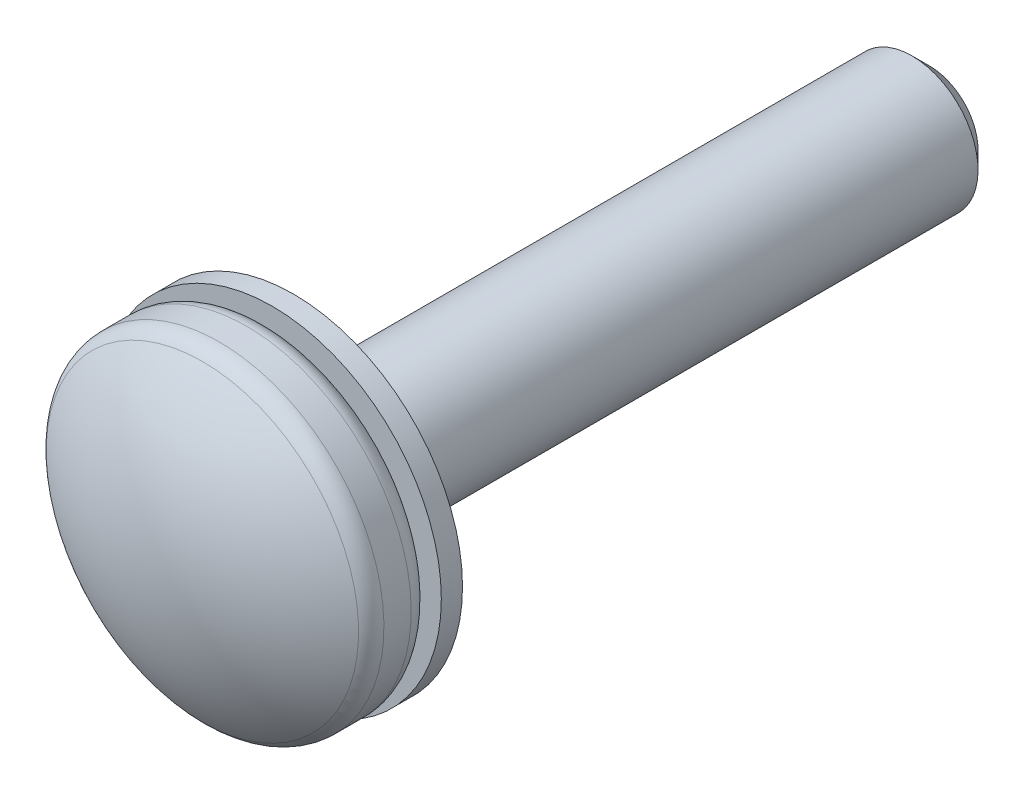
SolidWorks part; units mm, degrees
material "AISI 304"
ref_plane "Front Plane" through (0, 0, 0) normal (0, 0, 1) x (1, 0, 0)
ref_plane "Top Plane" through (0, 0, 0) normal (0, 1, 0) x (1, 0, 0)
ref_plane "Right Plane" through (0, 0, 0) normal (1, 0, 0) x (0, 0, -1)
sketch "Sketch1" plane through (0, 0, 0) normal (0, 0, 1) x (1, 0, 0)
  circle A0 centre (0, 0) radius 2.413
  dimension "decimal equ" = 4.826
curve "Helix/Spiral1" pitch 0.7937 height 19.8438 turns 25 parameters "helix length"=19.8438, "pitch"=0.7937
sketch "Sketch2" plane through (0, 0, 0) normal (1, 0, 0) x (0, 0, -1)
  line L0 (0.2977, 2.413) -> (0.3969, 2.413)
  line L1 (0.3969, 2.413) -> (0.6945, 1.8974)
  line L2 (0.2977, 2.413) -> (0, 1.8974)
  line L3 (0, 1.8974) -> (0.6945, 1.8974)
  line L4 (0, 1.8974) -> (0, 2.413) construction
  line L5 (0, 2.413) -> (0, -2.413) construction
  line L6 (0.1488, 2.1552) -> (0.5457, 2.1552) construction
  line L7 (0, 2.413) -> (0, -2.413) construction
  line L8 (0.3473, 2.413) -> (0.3473, 1.8974) construction
  point P6 (-3.175, -2.413)
  dimension "D1" = 60
  dimension "D3" = 0.0992
  dimension "D4" = 0.3969
  dimension "D2" = 3.175
sketch "Sketch3" plane through (0, 0, 0) normal (1, 0, 0) x (0, 0, -1)
  line L0 (0, 0) -> (-19.05, 0) construction
  line L1 (0, 1.8974) -> (0.6945, 1.8974) construction
  line L2 (0, 0) -> (-19.05, 0)
  line L3 (0, 0) -> (0, 1.8974)
  line L4 (0, 1.8974) -> (-19.05, 1.8974)
  line L5 (-19.05, 0) -> (-19.05, 1.8974)
  dimension "length" = 19.05
revolve "Revolve1" add sketch "Sketch3" angle 360 about L0
sweep "Sweep1" [suppressed] add profiles "Sketch2" path "Helix/Spiral1"
sketch "Sketch33" [suppressed] plane through (0, 0, 0) normal (0, 0, -1) x (-1, 0, 0)
  circle A1 centre (0, 0) radius 2.413
extrude "Extrude6" [suppressed] cut sketch "Sketch33" along normal through all
sketch "Sketch34" [suppressed] plane through (0, 0, 0) normal (0, 0, -1) x (-1, 0, 0)
  circle A0 centre (0, 0) radius 1.8974 construction
  circle A1 centre (0, 0) radius 1.8026
  dimension "D2" = 3.6051
extrude "Extrude7" [suppressed] cut sketch "Sketch34" against normal through all draft 45 flip side to cut
sketch "Sketch10" plane through (0, 0, 0) normal (1, 0, 0) x (0, 0, -1)
  line L0 (0, 0) -> (23.0169, 0) construction
  line L1 (-273.05, 12.7) -> (-19.05, 12.7)
  line L2 (-273.05, 12.7) -> (-273.05, 0)
  line L3 (-273.05, 0) -> (-19.05, 0)
  line L4 (-19.05, 12.7) -> (-19.05, 0)
  line L5 (-19.05, 0) -> (-19.05, 1.8974) construction
  dimension "D1" = 254
  dimension "D2" = 12.7
revolve "Cut-Revolve2" [suppressed] cut sketch "Sketch10" angle 360 about L0
sketch "Sketch35" plane through (0, 0, 0) normal (1, 0, 0) x (0, 0, -1)
  line L0 (-19.05, 2.413) -> (-19.05, 1.8974)
  line L1 (-19.05, 1.8974) -> (-18.1356, 1.8974)
  line L2 (-18.1356, 1.8974) -> (-17.62, 2.413)
  line L3 (-19.05, 2.413) -> (-17.62, 2.413)
  dimension "D1" = 45
  dimension "D2" = 0.9144
revolve "Cut-Revolve4" [suppressed] cut sketch "Sketch35" angle 360 about L2
sketch "Sketch8" plane through (0, 0, 0) normal (1, 0, 0) x (0, 0, -1)
  line L0 (0, 0) -> (-6.2449, 0) construction
  line L1 (-22.4282, 0) -> (-19.05, 0)
  line L2 (-22.4282, 0) -> (-22.4282, 4.7371)
  line L3 (-22.4282, 4.7371) -> (-19.05, 4.7371)
  line L4 (-19.05, 0) -> (-19.05, 4.7371)
  line L5 (-22.4282, -4.7371) -> (-19.05, -4.7371) construction
  line L6 (-19.05, 0) -> (-19.05, 1.8974) construction
  dimension "head dia" = 9.4742
  dimension "head height" = 3.3782
revolve "Revolve2" add sketch "Sketch8" angle 360 about L0
sketch "Sketch11" plane through (0, 0, 0) normal (1, 0, 0) x (0, 0, -1)
  line L0 (-20.7391, 4.7371) -> (-20.7391, -4.0894) construction
  line L1 (-22.4282, 0) -> (-6.8951, 0) construction
  line L2 (-22.4282, 4.7371) -> (-19.05, 4.7371) construction
  line L3 (-22.4282, 0) -> (-22.4282, 4.7371) construction
  line L4 (-20.4431, 4.7371) -> (-19.6581, 4.7371)
  line L6 (-19.05, 0) -> (-19.05, 4.7371) construction
  line L7 (-19.05, 4.129) -> (-18.415, 4.129)
  line L8 (-18.415, 4.129) -> (-18.415, 5.3721)
  line L9 (-18.415, 5.3721) -> (-23.0632, 5.3721)
  line L10 (-23.0632, 5.3721) -> (-23.0632, 0)
  line L11 (-23.0632, 0) -> (-22.4282, 0)
  arc A0 (-20.9295, 4.494) -> (-22.4282, 0) centre (-14.941, 0) ccw
  arc A1 (-19.05, 4.129) -> (-19.6581, 4.7371) centre (-19.6581, 4.129) ccw
  arc A2 (-20.9295, 4.494) -> (-20.4431, 4.7371) centre (-20.4431, 4.129) cw
  dimension "D1" = 0.6081
  dimension "D2" = 0.635
  dimension "D3" = 0.635
  dimension "D4" = 0.635
revolve "Cut-Revolve3" cut sketch "Sketch11" angle 360 about L1
ref_plane "Plane1" through (0, 0, 22.4282) normal (0, 0, 1) x (1, 0, 0)
sketch "Sketch12" plane through (0, 0, 22.4282) normal (0, 0, 1) x (1, 0, 0)
  line L0 (0.508, 2.3264) -> (0.508, 1.1906)
  line L1 (0.508, 1.1906) -> (1.1906, 0.508) construction
  line L2 (1.1906, 0.508) -> (2.3264, 0.508)
  line L3 (0, 2.3813) -> (0, 0)
  line L4 (0, 0) -> (2.3813, 0)
  line L5 (0, 0) -> (0, 4.7371) construction
  line L6 (0, 0) -> (0.8493, 0.8493) construction
  line L7 (1.1906, 0) -> (1.1906, 1.5633) construction
  line L8 (0.508, 1.1906) -> (0.7079, 0.7079)
  line L9 (1.1906, 0.508) -> (0.7079, 0.7079)
  line L10 (0, 0) -> (0, -1.0114) construction
  line L11 (-0.508, 2.3264) -> (-0.508, 1.1906) construction
  arc A0 (2.3813, 0) -> (2.3264, 0.508) centre (0, 0) ccw
  arc A1 (0.508, 2.3264) -> (0, 2.3813) centre (0, 0) ccw
  arc A2 (-2.3813, 0) -> (-2.3264, 0.508) centre (0, 0) cw construction
  dimension "phillips dia" = 4.7625
  dimension "D2" = 45
  dimension "D4" = 22.5
  dimension "slot width" = 1.016
extrude "Cut-Extrude1" [suppressed] cut sketch "Sketch12" against normal blind 2.8715
draft "Draft3" [suppressed] type of draft neutral plane draft angle 15 neutral plane "Plane1" faces to draft 2 parameters "D1"=15
draft "Draft4" [suppressed] type of draft neutral plane draft angle 5 neutral plane "Plane1" faces to draft 4 parameters "D1"=5
pattern_circular "CirPattern1" [suppressed] count 4 over 360 about axis through (0, 0, 22.4282) along (0, 0, -1) of bodies 110
ref_plane "Plane8" through (0, 0, 18.9187) normal (0, 0, -1) x (-1, 0, 0)
sketch "Sketch18" plane through (0, 0, 18.9187) normal (0, 0, 1) x (1, 0, 0)
  line L0 (0, -1.8974) -> (0, -4.8641) construction
  circle A0 centre (0, 0) radius 4.8641
  circle A1 centre (0, 0) radius 1.8974 construction
  circle A3 centre (0, 0) radius 3.3808
  point P10 (0, -3.3808)
  dimension "washer dia." = 9.7282
  dimension "D1" = 2.9667
  dimension "D2" = 1.4833
extrude "Extrude1" add sketch "Sketch18" against normal blind 0.6096 separate body
sketch "Sketch19" plane through (0, 0, 18.3091) normal (0, 0, -1) x (-1, 0, 0)
  line L0 (0, 0) -> (0, 8.8432) construction
  line L1 (1.3953, 3.5272) -> (0, 0)
  line L2 (0.9883, 3.6882) -> (0, 0) construction
  line L3 (0.5552, 3.7523) -> (0, 0)
  line L4 (0.4948, 3.3444) -> (1.2436, 3.1437) construction
  arc A0 (1.3953, 3.5272) -> (0.5552, 3.7523) centre (0.9883, 3.6882) ccw
  circle A1 centre (0, 0) radius 3.3808 construction
  circle A5 centre (0, 0) radius 4.2561
  circle A6 centre (0, 0) radius 4.2561 construction
  dimension "D2" = 0.8755
  dimension "D3" = 15
extrude "Cut-Extrude2" [suppressed] cut sketch "Sketch19" against normal through all
pattern_circular "CirPattern2" [suppressed] count 12 over 360 of bodies 119
ref_plane "Plane6" [suppressed] through (0, 3.3444, 0) normal (0, 1, 0) x (-1, 0, 0)
sketch "Sketch25" [suppressed] plane through (0, 3.3444, 0) normal (0, 1, 0) x (-1, 0, 0)
  line L2 (-0.4948, 18.6139) -> (0.4948, 18.6139) construction
  line L4 (-0.4948, 18.3091) -> (0.4948, 18.3091)
  line L5 (-0.4948, 18.3091) -> (-0.4948, 18.9187)
  line L6 (-0.4948, 18.9187) -> (0.4948, 18.9187)
  line L7 (0.4948, 18.3091) -> (0.4948, 18.9187)
  line L14 (0, 18.6139) -> (0, 18.3091) construction
ref_plane "Plane7" [suppressed] through (0, 1.8974, 0) normal (0, 1, 0) x (-1, 0, 0)
sketch "Sketch26" [suppressed] plane through (0, 1.8974, 0) normal (0, 1, 0) x (-1, 0, 0)
  line L0 (-0.4781, 18.4931) -> (-0.2301, 19.05)
  line L1 (-0.4781, 18.4931) -> (0.2301, 18.1778)
  line L2 (-0.2301, 19.05) -> (0.4781, 18.7347)
  line L3 (0.2301, 18.1778) -> (0.4781, 18.7347)
  line L7 (-0.3541, 18.7716) -> (0.3541, 18.4562) construction
  line L8 (-0.124, 18.3354) -> (0, 18.6139) construction
  line L9 (-0.2301, 19.05) -> (-0.2301, 18.9187) construction
  line L11 (4.8641, 18.9187) -> (-4.8641, 18.9187) construction
  line L13 (0.4781, 18.9187) -> (-0.2301, 18.9187) construction
  line L14 (-0.4948, 18.3091) -> (-0.4948, 18.9187) construction
  line L15 (-0.4948, 18.6139) -> (0.4948, 18.6139) construction
  dimension "D1" = 0.7752
  dimension "D3" = 24
loft "Loft4" [suppressed] add profiles "Sketch25", "Sketch26"
sketch "Sketch30" [suppressed] plane through (0, 3.3444, 0) normal (0, 1, 0) x (-1, 0, 0)
  line L4 (-0.4948, 18.3091) -> (0.4948, 18.3091)
  line L5 (-0.4948, 18.3091) -> (0.4948, 18.3091)
  line L6 (0.4948, 18.3091) -> (0.4948, 18.9187)
  line L7 (0.4948, 18.3091) -> (0.4948, 18.9187)
  line L8 (0.4948, 18.9187) -> (-0.4948, 18.9187)
  line L9 (0.4948, 18.9187) -> (-0.4948, 18.9187)
  line L10 (-0.4948, 18.9187) -> (-0.4948, 18.3091)
  line L11 (-0.4948, 18.9187) -> (-0.4948, 18.3091)
  dimension "D1" = 0
extrude "Extrude5" [suppressed] add sketch "Sketch30" along normal blind 0.0508 separate body
pattern_circular "CirPattern8" [suppressed] count 12 over 360 of bodies 182 144
combine bodies "Combine2" [suppressed] operation type add bodies to combine 144 182 187 188 189 190 191 192 193 194 195 196 197 198 199 200 201 202 203 204 205 206 207 208 120
chamfer "Chamfer1" distance 0.508 angle 45 1 edges at (0, 1.8974, 0)
equation "\"D3@Sketch2\" = \"pitch@Helix/Spiral1\"*.125"
equation "\"D4@Sketch2\" = \"pitch@Helix/Spiral1\"*.5"
equation "\"D1@Sketch11\" = \"head height@Sketch8\"*.18"
equation "\"D1@Cut-Extrude1\" = \"head height@Sketch8\"*.85"
equation "\"D2@Sketch19\" = \"washer dia.@Sketch18\"*.09"
equation "\"D1@Sketch19\" = \"washer dia.@Sketch18\"*.0625"
equation "\"helix length@Helix/Spiral1\" = \"length@Sketch3\" + \"pitch@Helix/Spiral1\""
equation "\"D2@Sketch34\" = \"D1@Sketch34\"*.95"
equation "\"D1@Plane8\" = \"D2@Sketch26\""
equation "\"D2@Sketch2\" = \"pitch@Helix/Spiral1\"*4"
equation "\"D2@Sketch35\" = \"washer width@Extrude1\"*1.5"
equation "\"D2@Sketch18\" = \"D1@Sketch18\"/2"
equation "\"D1@Sketch26\" = \"D4@Sketch19\""
